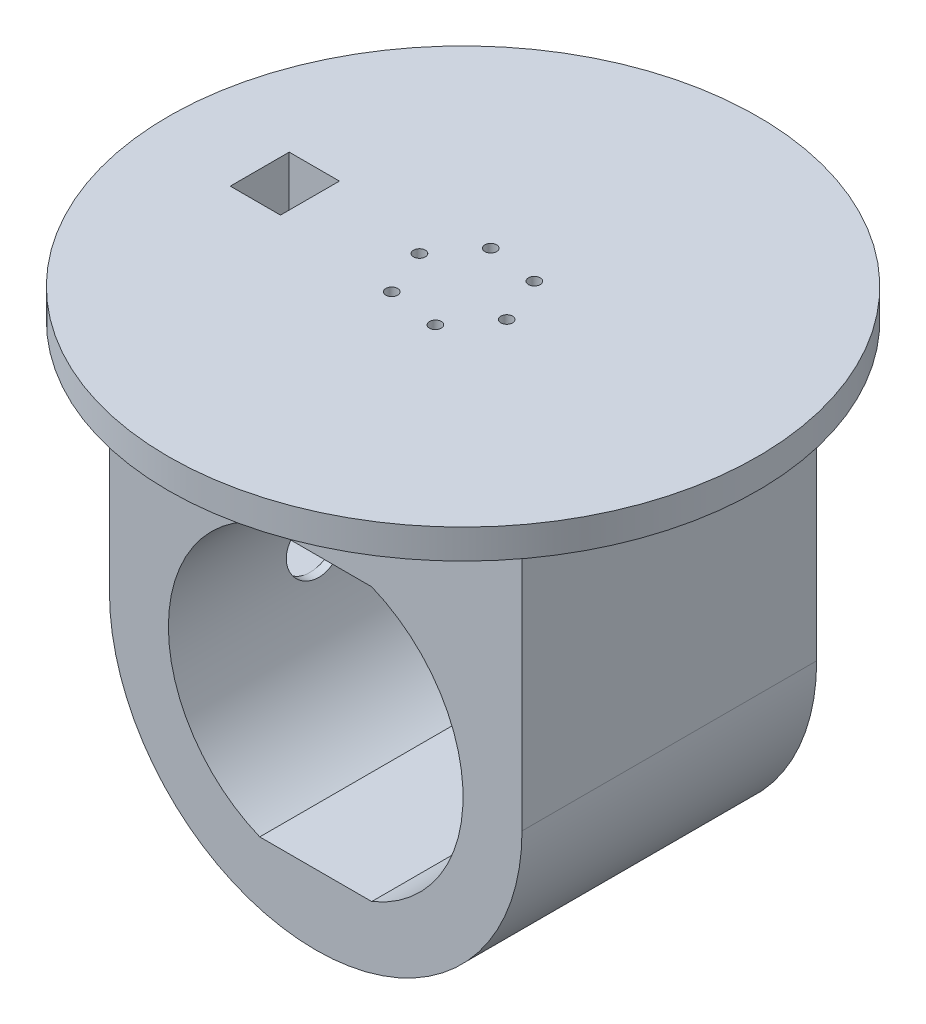
SolidWorks part; units mm, degrees
ref_plane "前视基准面" through (0, 0, 0) normal (0, 0, 1) x (1, 0, 0)
ref_plane "上视基准面" through (0, 0, 0) normal (0, 1, 0) x (1, 0, 0)
ref_plane "右视基准面" through (0, 0, 0) normal (1, 0, 0) x (0, 0, -1)
sketch "草图1" plane through (0, 0, 0) normal (0, 1, 0) x (1, 0, 0)
  circle A0 centre (0, 0) radius 100
extrude "凸台-拉伸1" add sketch "草图1" along normal blind 10
sketch "草图2" plane through (0, 0, 0) normal (0, 1, 0) x (1, 0, 0)
  line L1 (-70, -50) -> (70, -50)
  line L2 (-70, -50) -> (-70, 50)
  line L3 (-70, 50) -> (70, 50)
  line L4 (70, -50) -> (70, 50)
  line L5 (-70, -50) -> (70, 50) construction
  line L6 (-70, 50) -> (70, -50) construction
  point P0 (0, 0)
extrude "凸台-拉伸2" add sketch "草图2" against normal blind 160
fillet "圆角1" radius 70 1 edges at (-70, -160, 0)
fillet "圆角2" radius 70 1 edges at (70, -160, 0)
sketch "草图3" plane through (0, 0, -50) normal (0, 0, -1) x (-1, 0, 0)
  line L0 (0, 0) -> (0, -269.1663) construction
  circle A1 centre (0, -90) radius 50
extrude "切除-拉伸1" cut sketch "草图3" against normal blind 160
sketch "草图9" plane through (0, 0, -50) normal (0, 0, -1) x (-1, 0, 0)
  line L0 (-26.309, -136.25) -> (26.9963, -136.25)
  line L1 (-23.874, -43.75) -> (22.2985, -43.75)
  line L8 (22.2985, -43.75) -> (22.2985, -37.8171)
  line L9 (22.2985, -37.8171) -> (-23.874, -37.8171)
  line L10 (-23.874, -37.8171) -> (-23.874, -43.75)
  line L11 (-26.309, -136.25) -> (-26.309, -145.5353)
  line L12 (-26.309, -145.5353) -> (26.9963, -145.5353)
  line L13 (26.9963, -145.5353) -> (26.9963, -136.25)
  dimension "D1" = 92.5
sketch "草图13" plane through (-70, 0, 0) normal (-1, 0, 0) x (0, 0, 1)
  line L3 (-50, -90) -> (50, -90) construction
  circle A0 centre (0, -90) radius 10
extrude "切除-拉伸5" cut sketch "草图13" against normal blind 25 from offset 1 offset against normal yes
extrude "凸台-拉伸3" add sketch "草图9" against normal blind 100
sketch "草图14" plane through (0, 0, -50) normal (0, 0, -1) x (-1, 0, 0)
  circle A0 centre (0, -90) radius 50
extrude "切除-拉伸6" cut sketch "草图14" against normal blind 7.7
sketch "草图15" plane through (0, 10, 0) normal (0, 1, 0) x (1, 0, 0)
  line L0 (-69, -10) -> (-50, -10) construction
  line L1 (-69, 10) -> (-51.9634, 10)
  line L2 (-69, 10) -> (-69, -10)
  line L3 (-69, -10) -> (-51.9634, -10)
  line L4 (-51.9634, 10) -> (-51.9634, -10)
extrude "切除-拉伸7" cut sketch "草图15" against normal blind 110
sketch "草图16" plane through (0, 10, 0) normal (0, 1, 0) x (1, 0, 0)
  circle A0 centre (10.538, 13.657) radius 2
  circle A1 centre (17.0963, -2.2977) radius 2
  circle A2 centre (6.5583, -15.9547) radius 2
  circle A3 centre (-10.538, -13.657) radius 2
  circle A4 centre (-17.0963, 2.2977) radius 2
  circle A5 centre (-6.5583, 15.9547) radius 2
  point P16 (0, 0)
  dimension "D1" = 17.25
  dimension "D2" = 6
extrude "切除-拉伸8" cut sketch "草图16" against normal blind 10
